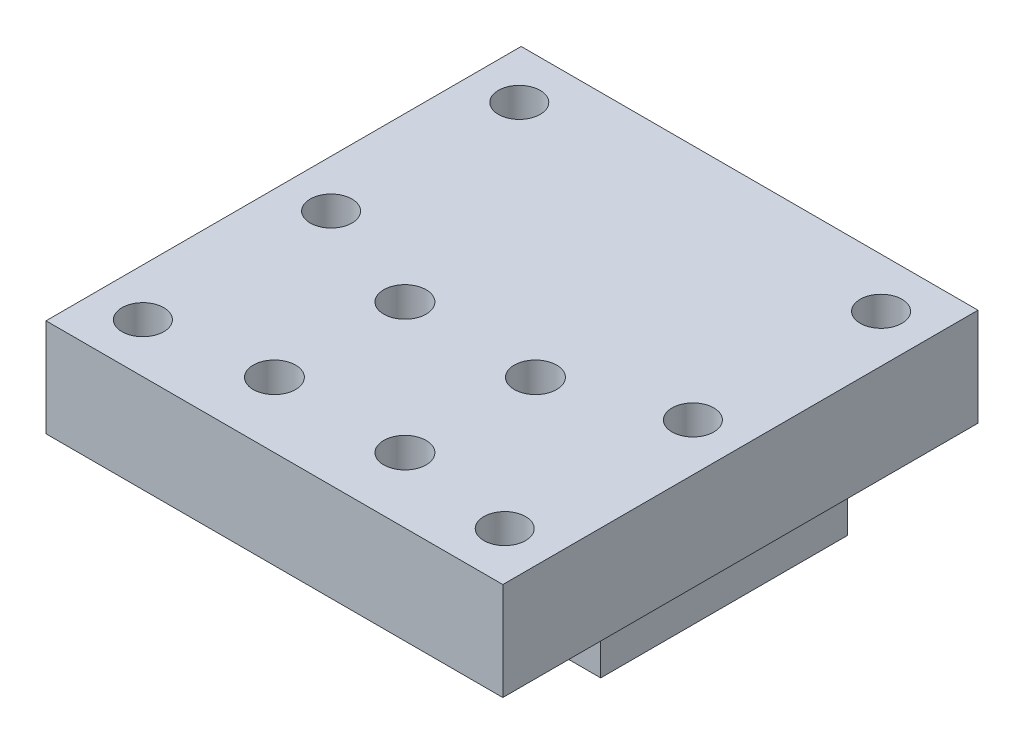
SolidWorks part; units mm, degrees
ref_plane "Front Plane" through (0, 0, 0) normal (0, 0, 1) x (1, 0, 0)
ref_plane "Top Plane" through (0, 0, 0) normal (0, 1, 0) x (1, 0, 0)
ref_plane "Right Plane" through (0, 0, 0) normal (1, 0, 0) x (0, 0, -1)
sketch "Sketch1" plane through (0, 0, 0) normal (0, 1, 0) x (1, 0, 0)
  line L1 (-35, 20) -> (35, 20)
  line L2 (-35, 20) -> (-35, -20)
  line L3 (-35, -20) -> (35, -20)
  line L4 (35, 20) -> (35, -20)
  line L5 (-35, 20) -> (35, -20) construction
  line L6 (-35, -20) -> (35, 20) construction
  line L7 (-10, 10) -> (10, 10) construction
  line L8 (-10, 10) -> (-10, -10) construction
  line L9 (-10, -10) -> (10, -10) construction
  line L10 (10, 10) -> (10, -10) construction
  line L11 (-10, 10) -> (10, -10) construction
  line L12 (-10, -10) -> (10, 10) construction
  circle A0 centre (10, 10) radius 1.6
  circle A1 centre (10, -10) radius 1.6
  circle A2 centre (-10, -10) radius 1.6
  circle A3 centre (-10, 10) radius 1.6
  point P0 (0, 0)
  point P5 (0, 0)
  point P21 (0, 0)
  dimension "D3" = 3.2
  dimension "D1" = 20
  dimension "D2" = 20
  dimension "D5" = 70
  dimension "D6" = 40
  dimension "D4" = 4
extrude "Boss-Extrude1" add sketch "Sketch1" along normal blind 15
sketch "Sketch2" plane through (0, 15, 0) normal (0, 1, 0) x (1, 0, 0)
  circle A0 centre (10, 10) radius 3.25
  circle A1 centre (10, -10) radius 3.25
  circle A2 centre (-10, -10) radius 3.25
  circle A3 centre (-10, 10) radius 3.25
  point P12 (0, 0)
  dimension "D1" = 6.5
  dimension "D2" = 4
extrude "Cut-Extrude1" cut sketch "Sketch2" against normal offset from surface (5 mm away) 10 up to face at (0, 0, 0)
sketch "Sketch3" plane through (0, 15, 0) normal (0, 1, 0) x (1, 0, 0)
  line L0 (35, 20) -> (-35, 20) construction
  line L5 (-35, 15) -> (35, 15)
  line L6 (-35, 15) -> (-35, 52.813)
  line L7 (-35, 52.813) -> (35, 52.813)
  line L8 (35, 15) -> (35, 52.813)
  line L9 (35, -20) -> (35, 20) construction
  line L10 (-35, 20) -> (-35, -20) construction
  dimension "D1" = 37.813
  dimension "D2" = 5
extrude "Boss-Extrude2" add sketch "Sketch3" against normal blind 39.8969
fillet "Fillet1" radius 2 1 edges at (0, 0, -15)
sketch "Sketch4" plane through (0, 15, 0) normal (0, 1, 0) x (1, 0, 0)
  line L0 (-35, 52.813) -> (35, -20) construction
  line L1 (-35, -20) -> (35, -20) construction
  line L2 (35, -20) -> (35, 52.813) construction
  line L3 (-35, -20) -> (35, 52.813) construction
  line L4 (0, 16.4065) -> (0, 35.737) construction
  line L5 (0, 16.4065) -> (23.279, 16.4065) construction
  line L6 (27.7218, 45.2423) -> (27.7218, -12.4293) construction
  circle A0 centre (27.7218, 45.2423) radius 3.2
  circle A1 centre (-27.7218, 45.2423) radius 3.2
  circle A2 centre (-27.7218, -12.4293) radius 3.2
  circle A3 centre (27.7218, -12.4293) radius 3.2
  circle A4 centre (27.7218, 16.4065) radius 3.2
  circle A5 centre (-27.7218, 16.4065) radius 3.2
  point P14 (0, 16.4065)
  dimension "D1" = 6.4
  dimension "D2" = 40
extrude "Cut-Extrude2" cut sketch "Sketch4" against normal blind 8
sketch "Sketch5" plane through (0, -24.8969, 0) normal (0, -1, 0) x (1, 0, 0)
  line L0 (-35, -52.813) -> (-35, -15) construction
  line L1 (-35, -30.9065) -> (35, -30.9065) construction
  line L2 (-35, -30.9065) -> (-35, -36.9065) construction
  line L3 (-35, -36.9065) -> (35, -36.9065) construction
  line L4 (35, -30.9065) -> (35, -36.9065) construction
  line L5 (35, -15) -> (35, -52.813) construction
  line L6 (-35, -33.9065) -> (35, -33.9065) construction
  line L7 (0, -22.9065) -> (0, -44.9065) construction
  circle A0 centre (0, -22.9065) radius 3.2
  circle A1 centre (0, -44.9065) radius 3.2
  circle A2 centre (-22, -22.9065) radius 3.2
  circle A3 centre (-22, -44.9065) radius 3.2
  point P10 (35, -33.9065)
  point P11 (0, -33.9065)
  dimension "D2" = 8
  dimension "D3" = 6.4
  dimension "D5" = 22
  dimension "D1" = 6
  dimension "D4" = 11
extrude "Cut-Extrude3" cut sketch "Sketch5" against normal blind 10
sketch "Sketch7" plane through (0, -24.8969, 0) normal (0, -1, 0) x (1, 0, 0)
  line L0 (35, -52.813) -> (-35, -52.813) construction
  line L1 (35, -13) -> (15, -13)
  line L2 (35, -13) -> (35, -52.813)
  line L3 (35, -52.813) -> (15, -52.813)
  line L4 (15, -13) -> (15, -52.813)
  point P7 (35, -13)
  dimension "D1" = 20
extrude "Cut-Extrude4" cut sketch "Sketch7" against normal up to surface (24.8969 mm away) up to face at (0, 0, 3.5)
fillet "Fillet2" radius 2 1 edges at (15, 0, -32.9065)
